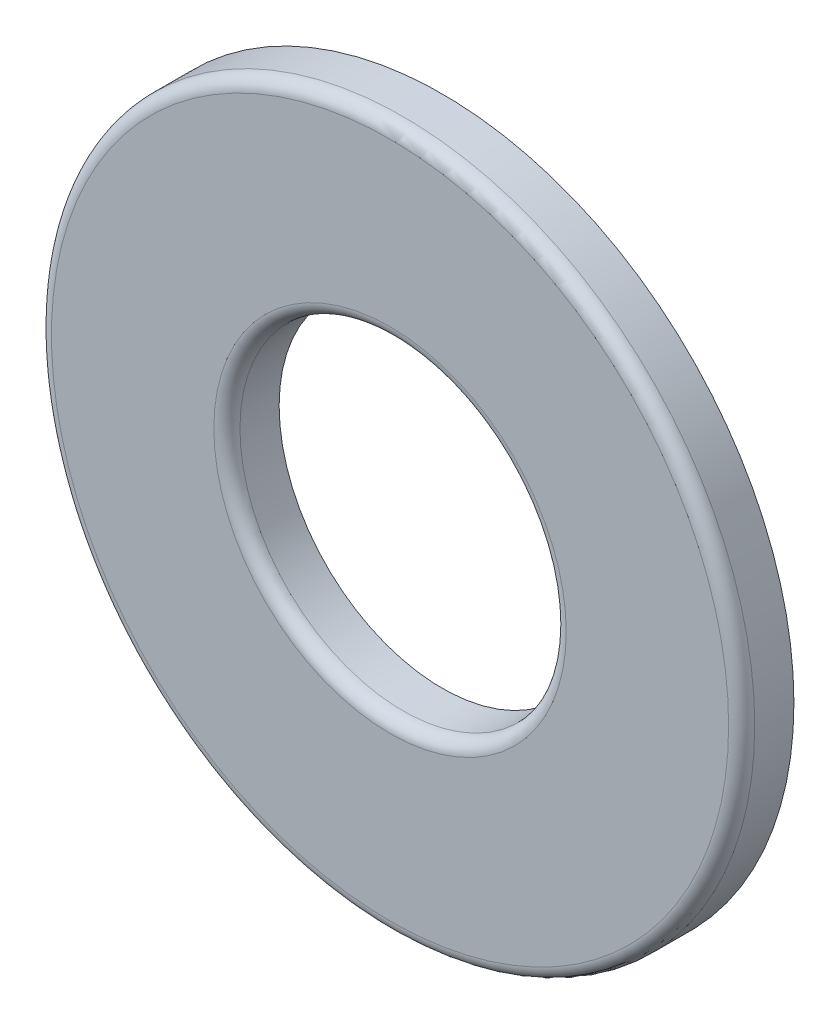
SolidWorks part; units mm, degrees
note: '?' marks a value the reader was unsure of.
other "Imported1" parameters "D1"=0.2064, "TH"=1.0287, "Thickness"=0.8255
ref_plane "Front Plane" through (0, 0, 0) normal (0, 0, 1) x (1, 0, 0)
ref_plane "Top Plane" through (0, 0, 0) normal (0, 1, 0) x (1, 0, 0)
ref_plane "Right Plane" through (0, 0, 0) normal (1, 0, 0) x (0, 0, -1)
sketch "Sketch1" plane through (0, 0, 0) normal (0, 0, 1) x (1, 0, 0)
  line L0 (-5.5562, 0) -> (5.5562, 0) construction
  line L1 (-2.5781, 0) -> (2.5781, 0) construction
  circle A0 centre (0, 0) radius 2.5781 construction
  circle A1 centre (0, 0) radius 5.5562 construction
  point P8 (0, 0)
  point P9 (0, 5.5562)
  point P11 (2.5781, 0)
  dimension "ID" = 5.1562
  dimension "OD" = 11.1125
sketch "Sketch2" plane through (0, 0, 0) normal (1, 0, 0) x (0, 0, -1)
  line L0 (-0.4127, 5.5562) -> (0.4128, 5.5562) construction
  point P2 (0, 5.5562)
sketch "Sketch3" plane through (0, 0, 0) normal (0, 0, 1) x (1, 0, 0)
  circle A0 centre (0, 0) radius 2.5781
  circle A1 centre (0, 0) radius 5.5562
extrude "Boss-Extrude1" add sketch "Sketch3" along normal up to vertex (0.4128 mm away) and the other way up to vertex (0.4128 mm away) up to point (0, 5.5562, 0.4127) other way up to point (0, 5.5562, -0.4128)
fillet "Fillet1" radius 0.2064 2 edges at (5.5562, 0, 0.4127) (2.5781, 0, 0.4127)
ref_axis "Center Axis 1" through (0, 0, 0.2064) along (0, 0, -1)?
equation "\"D1@Fillet1\"=\"Thickness@Sketch2\"/4"
